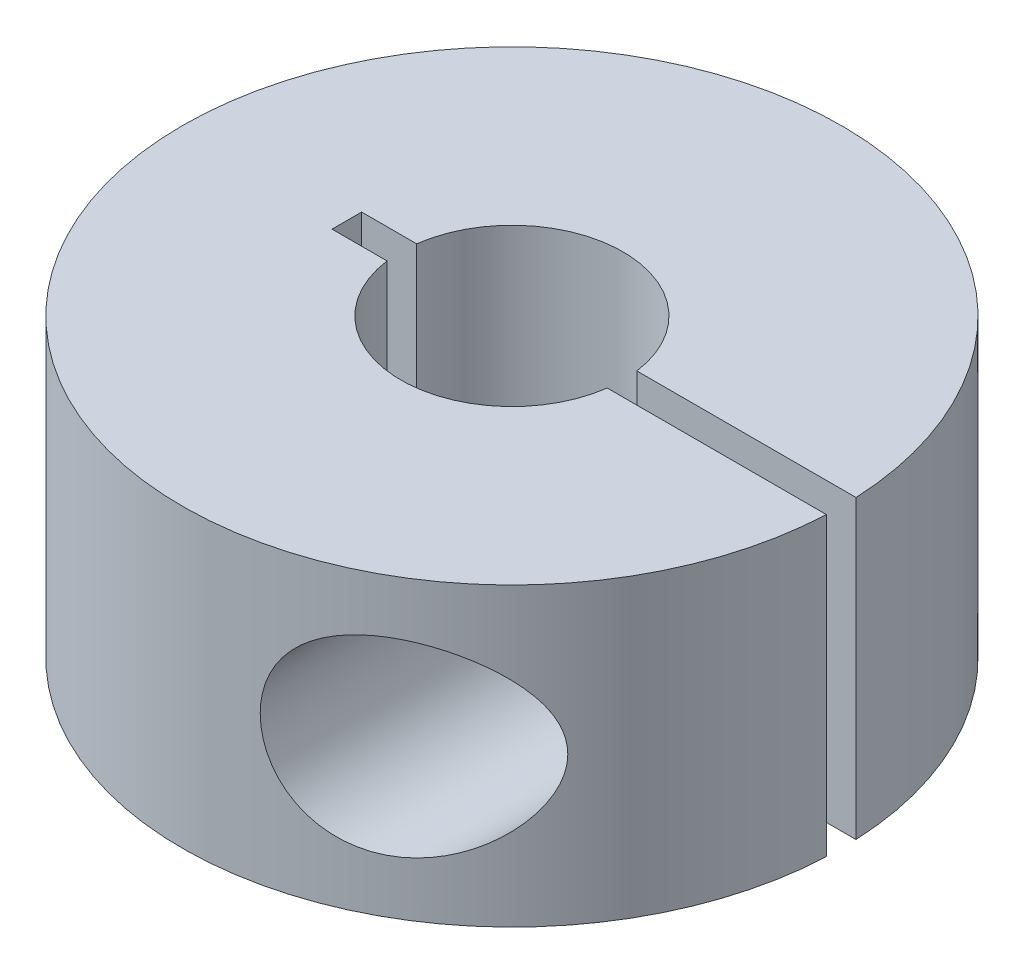
SolidWorks part; units mm, degrees
ref_plane "Front Plane" through (0, 0, 0) normal (0, 0, 1) x (1, 0, 0)
ref_plane "Top Plane" through (0, 0, 0) normal (0, 1, 0) x (1, 0, 0)
ref_plane "Right Plane" through (0, 0, 0) normal (1, 0, 0) x (0, 0, -1)
sketch "Sketch1" plane through (0, 0, 0) normal (0, 1, 0) x (1, 0, 0)
  circle A0 centre (0, 0) radius 11.125
  dimension "D1" = 22.25
extrude "Boss-Extrude1" add sketch "Sketch1" along normal blind 10
ref_plane "Plane1" through (0, 0, -3) normal (0, 0, 1) x (1, 0, 0)
sketch "Sketch2" plane through (0, 0, -3) normal (0, 0, 1) x (1, 0, 0)
  line L0 (0, 5) -> (11.125, 5) construction
  line L1 (11.125, 10) -> (-11.125, 10) construction
  line L2 (0, 0) -> (0, 10) construction
  line L3 (11.125, 0) -> (11.125, 10) construction
  line L5 (4.3581, 2.8954) -> (6.783, 2.9047)
  line L6 (6.783, 2.9047) -> (7.9874, 5.0093)
  line L7 (7.9874, 5.0093) -> (6.7669, 7.1046)
  line L8 (6.7669, 7.1046) -> (4.342, 7.0953)
  line L9 (4.342, 7.0953) -> (3.1376, 4.9907)
  line L10 (3.1376, 4.9907) -> (4.3581, 2.8954)
  circle A0 centre (5.5625, 5) radius 2.1 construction
  point P1 (0, 10)
  point P9 (5.5625, 5)
  dimension "D1" = 4.2
  dimension "D2" = 2.4249
extrude "Cut-Extrude1" cut sketch "Sketch2" against normal through all
sketch "Sketch3" plane through (0, 0, 0) normal (0, 1, 0) x (1, 0, 0)
  line L0 (-5.5735, 0.5) -> (-5.5735, -0.5)
  line L5 (-5.5735, -0.5) -> (11.4265, -0.5)
  line L6 (11.4265, -0.5) -> (11.4265, 0.5)
  line L12 (11.4265, 0.5) -> (-5.5735, 0.5)
  line L13 (-5.5735, 0) -> (11.4265, 0) construction
  point P3 (-0.5735, 0.5)
  point P7 (0, 0)
  dimension "D1" = 5
  dimension "D2" = 12
  dimension "D3" = 1
extrude "Cut-Extrude2" cut sketch "Sketch3" along normal through all
ref_plane "Plane2" through (0, 0, 4.6) normal (0, 0, 1) x (1, 0, 0)
sketch "Sketch6" plane through (0, 0, 4.6) normal (0, 0, 1) x (1, 0, 0)
  line L0 (0, 5) -> (11.125, 5) construction
  point P0 (5.5625, 5)
hole_wizard "CBORE for M2 Hex Head Machine Screw1" positions "Sketch6" profile "Sketch7" counterbore size "M2" standard "ANSI Metric" end condition through all
sketch "Sketch7" plane through (5.5625, 5, 4.6) normal (1, 0, 0) x (0, -1, 0)
  line L0 (0, 0) -> (0, 15.725)
  line L1 (0, 15.725) -> (1.2, 15.725)
  line L3 (1.2, 15.725) -> (1.2, 1.6)
  line L4 (1.2, 1.6) -> (3.19, 1.6)
  line L5 (3.19, 1.6) -> (3.19, 0)
  line L7 (3.19, 0) -> (0, 0)
  line L11 (0, -6.35) -> (0, 107.95) construction
  dimension "Thru Hole Dia." = 2.4
  dimension "Thru Hole Depth" = 15.725
  dimension "C'Bore Dia." = 6.38
  dimension "C'Bore Depth" = 1.6
sketch "Sketch8" plane through (0, 0, 4.6) normal (0, 0, 1) x (1, 0, 0)
  circle A0 centre (5.5625, 5) radius 3.19
  dimension "D1" = 6.38
extrude "Cut-Extrude3" cut sketch "Sketch8" along normal through all
sketch "Sketch9" plane through (0, 0, 0) normal (0, 1, 0) x (1, 0, 0)
  circle A0 centre (0, 0) radius 3.75
  dimension "AxleHoleDiameter" = 7.5
extrude "Cut-Extrude4" cut sketch "Sketch9" along normal through all both and the other way through all
